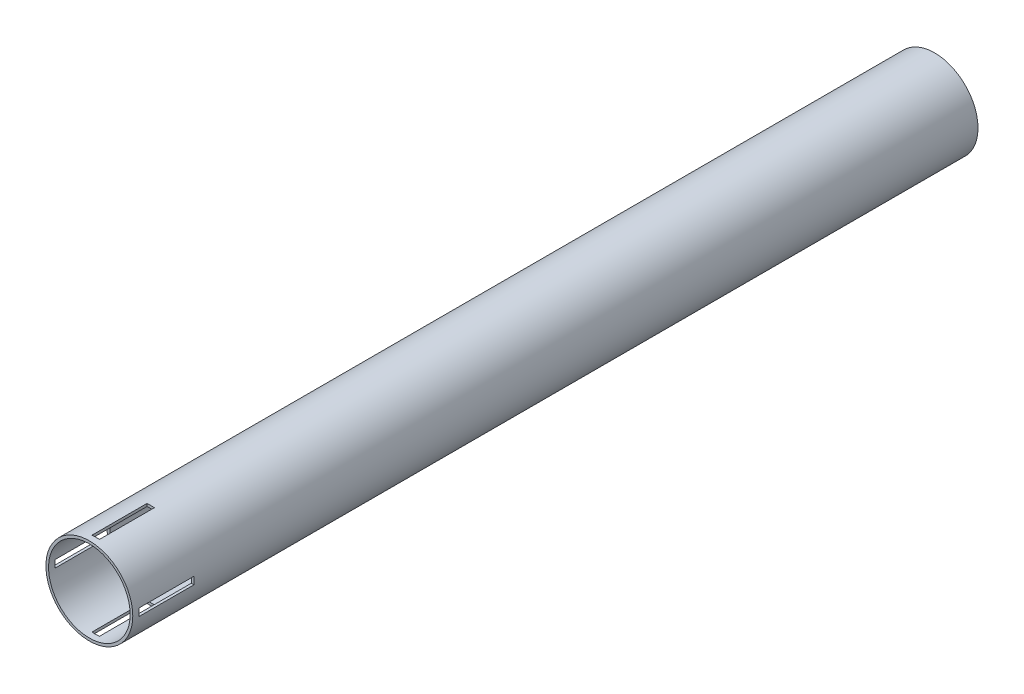
SolidWorks part; units mm, degrees
ref_plane "Front Plane" through (0, 0, 0) normal (0, 0, 1) x (1, 0, 0)
ref_plane "Top Plane" through (0, 0, 0) normal (0, 1, 0) x (1, 0, 0)
ref_plane "Right Plane" through (0, 0, 0) normal (1, 0, 0) x (0, 0, -1)
sketch "Sketch1" plane through (0, 0, 0) normal (0, 0, 1) x (1, 0, 0)
  circle A0 centre (0, 0) radius 20.555
  circle A1 centre (0, 0) radius 19.305
  dimension "D1" = 41.11
  dimension "D2" = 38.61
extrude "Boss-Extrude3" add sketch "Sketch1" against normal blind 400
sketch "Sketch2" plane through (0, 0, 0) normal (0, 1, 0) x (1, 0, 0)
  line L0 (0, -22.6105) -> (0, 22.6105) construction
  line L1 (-1.75, 29) -> (1.75, 29)
  line L2 (-1.75, 29) -> (-1.75, 3)
  line L3 (-1.75, 3) -> (1.75, 3)
  line L4 (1.75, 29) -> (1.75, 3)
  line L5 (-1.75, 29) -> (1.75, 3) construction
  line L6 (-1.75, 3) -> (1.75, 29) construction
  line L7 (-22.6105, 0) -> (22.6105, 0) construction
  point P0 (0, 16)
  dimension "D1" = 3.5
  dimension "D2" = 26
  dimension "D3" = 3
extrude "Cut-Extrude1" cut sketch "Sketch2" against normal through all both and the other way through all
pattern_circular "CirPattern1" count 2 over 90 about axis through (0, 0, -400) along (0, 0, 1) of "Cut-Extrude1" reverse direction yes
